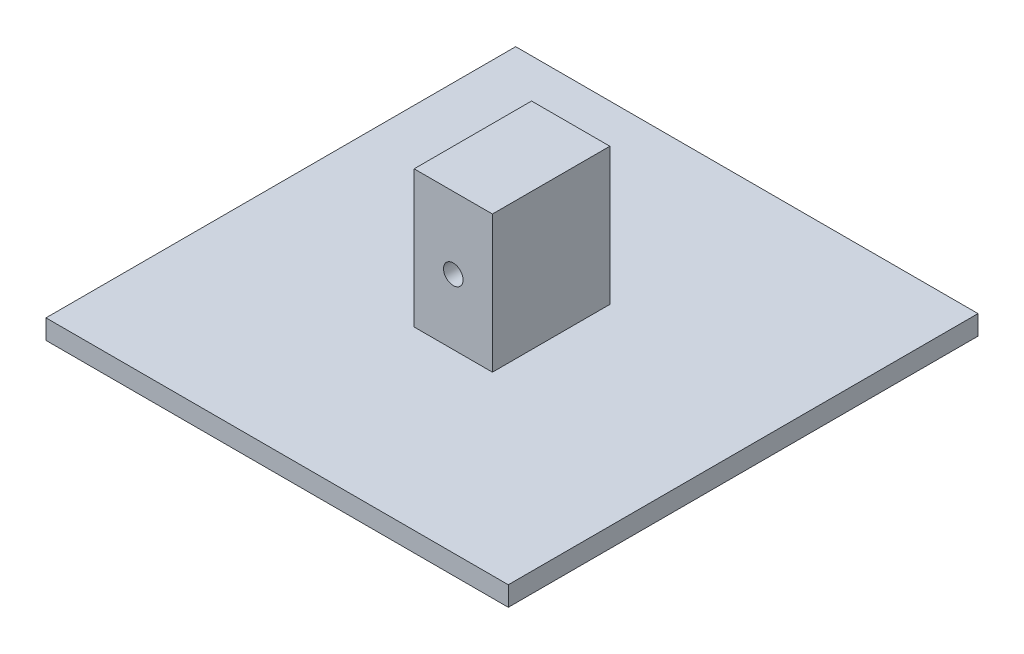
SolidWorks part; units mm, degrees
ref_plane "Front Plane" through (0, 0, 0) normal (0, 0, 1) x (1, 0, 0)
ref_plane "Top Plane" through (0, 0, 0) normal (0, 1, 0) x (1, 0, 0)
ref_plane "Right Plane" through (0, 0, 0) normal (1, 0, 0) x (0, 0, -1)
sketch "Sketch-Profile" plane through (0, 0, 0) normal (1, 0, 0) x (0, 0, -1)
  line L0 (-76.2, 6.35) -> (-76.2, 0)
  line L5 (-76.2, 6.35) -> (-19.05, 6.35)
  line L6 (-76.2, 0) -> (76.2, 0)
  line L7 (76.2, 6.35) -> (76.2, 0)
  line L8 (-76.2, 6.35) -> (76.2, 0) construction
  line L9 (-76.2, 0) -> (76.2, 6.35) construction
  line L10 (-19.05, 50.8) -> (-19.05, 6.35)
  line L11 (-19.05, 50.8) -> (19.05, 50.8)
  line L13 (19.05, 50.8) -> (19.05, 6.35)
  line L14 (-19.05, 50.8) -> (19.05, 6.35) construction
  line L15 (-19.05, 6.35) -> (19.05, 50.8) construction
  line L16 (19.05, 6.35) -> (76.2, 6.35)
  point P1 (0, 3.175)
  point P2 (0, 28.575)
  dimension "D1" = 6.35
  dimension "D2" = 50.8
  dimension "D3" = 152.4
  dimension "D4" = 38.1
extrude "Boss-Extrude1" add sketch "Sketch-Profile" along normal blind 12.7 and the other way blind 12.7
sketch "Sketch-Hole Location" plane through (0, 0, 19.05) normal (0, 0, 1) x (1, 0, 0)
  line L0 (0, 0) -> (0, 50.8) construction
  line L1 (12.7, 0) -> (-12.7, 0) construction
  line L2 (12.7, 50.8) -> (-12.7, 50.8) construction
  line L3 (109.3309, 27.5181) -> (22.8959, 27.5181) construction
  point P6 (0, 27.5181)
sketch "Sketch5" plane through (0, 0, 19.05) normal (0, 0, 1) x (1, 0, 0)
  point P0 (0, 27.5181)
hole_wizard "1/4 (0.25) Diameter Hole1" positions "Sketch5" profile "Sketch4" hole size "1/4" standard "ANSI Inch" end condition through all
sketch "Sketch4" plane through (0, 27.5181, 19.05) normal (1, 0, 0) x (0, -1, 0)
  line L0 (0, 0) -> (0, 95.25)
  line L1 (0, 95.25) -> (3.175, 95.25)
  line L2 (3.175, 95.25) -> (3.175, 0)
  line L5 (3.175, 0) -> (0, 0)
  line L11 (0, -6.35) -> (0, 107.95) construction
  dimension "Thru Hole Dia." = 6.35
  dimension "Thru Hole Depth" = 95.25
sketch "Sketch6" plane through (0, 0, 0) normal (1, 0, 0) x (0, 0, -1)
  line L0 (76.2, 0) -> (76.2, 6.35) construction
  line L1 (-76.2, 0) -> (76.2, 0) construction
  line L2 (-76.2, 6.35) -> (-76.2, 0) construction
  line L3 (76.2, 0) -> (76.2, 6.35)
  line L4 (-76.2, 0) -> (76.2, 0)
  line L5 (-76.2, 6.35) -> (-76.2, 0)
  line L6 (-76.2, 6.35) -> (76.2, 6.35)
extrude "Boss-Extrude2" add sketch "Sketch6" along normal blind 75 and the other way blind 75
